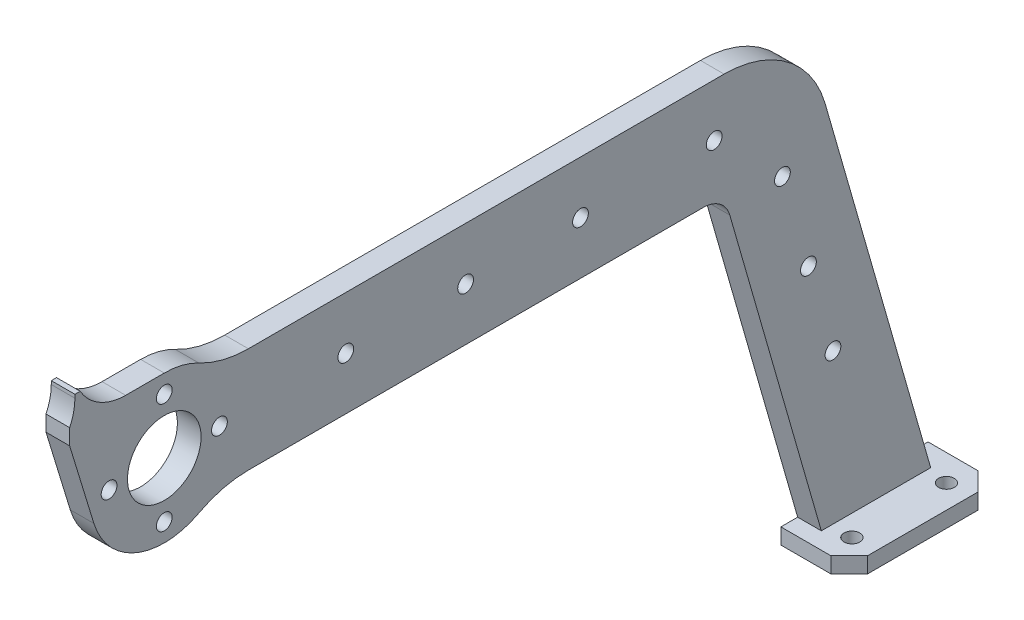
SolidWorks part; units mm, degrees
ref_plane "前视基准面" through (0, 0, 0) normal (0, 0, 1) x (1, 0, 0)
ref_plane "上视基准面" through (0, 0, 0) normal (0, 1, 0) x (1, 0, 0)
ref_plane "右视基准面" through (0, 0, 0) normal (1, 0, 0) x (0, 0, -1)
sketch "草图1" plane through (0, 0, 0) normal (1, 0, 0) x (0, 0, -1)
  line L2 (107.5854, -13.768) -> (125, -74.5)
  line L3 (125, -74.5) -> (145.806, -74.5)
  line L4 (145.806, -74.5) -> (125.7302, -4.4873)
  line L5 (106.5049, 10) -> (16, 10)
  line L7 (16, -10) -> (102.5851, -10)
  line L8 (135.8126, -75.9286) -> (111.4936, 8.8819) construction
  line L9 (0, 14) -> (-18, 14)
  line L10 (-18, 14) -> (-18, 11)
  line L11 (-18, 11) -> (-13.3889, -4.091)
  arc A0 (6.5882, 12.3529) -> (6.5882, -12.3529) centre (0, 0) ccw
  circle A1 centre (0, 0) radius 10.5 construction
  circle A2 centre (0, 0) radius 7
  circle A3 centre (0, 10.5) radius 1.5
  arc A7 (125.7302, -4.4873) -> (106.5049, 10) centre (106.5049, -10) ccw
  arc A8 (102.5851, -10) -> (107.5854, -13.768) centre (102.5851, -15.2018) cw
  arc A15 (16, 10) -> (6.5882, 12.3529) centre (16, 30) cw
  arc A16 (16, -10) -> (6.5882, -12.3529) centre (16, -30) ccw
  circle A17 centre (10.5, 0) radius 1.5
  circle A18 centre (0, -10.5) radius 1.5
  circle A19 centre (-10.5, 0) radius 1.5
  point P25 (0, 0)
  point P36 (135.403, -74.5)
  point P43 (9.798, 7.7889)
  point P50 (9.798, -10)
  dimension "D1" = 28
  dimension "D3" = 14
  dimension "D4" = 3
  dimension "D9" = 20
  dimension "D13" = 4
  dimension "D24" = 20
  dimension "D25" = 20
  dimension "D5" = 21
  dimension "D6" = 106
  dimension "D7" = 20
  dimension "D8" = 125
  dimension "D10" = 74.5
  dimension "D11" = 20
  dimension "D12" = 20.806
  dimension "D21" = 18
  dimension "D22" = 3
extrude "凸台-拉伸1" add sketch "草图1" along normal mid plane 4.5 contours A16 L7 A8 L2 L3 L4 A7 L5 A15 A0 A18 A17 A3 A2 | A0 L9 L10 L11 | A16 A0 region at (0, -9.5886, -106.815) region at (0, 9.7023, 13.097)
sketch "草图5" plane through (0, -74.5, 0) normal (0, -1, 0) x (1, 0, 0)
  line L0 (-2.25, -107.5854) -> (-2.25, -125) construction
  line L1 (-2.25, -121.806) -> (10.75, -121.806)
  line L2 (-2.25, -121.806) -> (-2.25, -149.806)
  line L3 (-2.25, -149.806) -> (10.75, -149.806)
  line L4 (10.75, -121.806) -> (10.75, -149.806)
  line L5 (2.25, -145.806) -> (-2.25, -145.806) construction
  dimension "D1" = 13
  dimension "D2" = 28
  dimension "D3" = 4
extrude "凸台-拉伸3" add sketch "草图5" along normal blind 3
sketch "草图6" plane through (0, -74.5, 0) normal (0, 1, 0) x (1, 0, 0)
  line L0 (10.75, 135.806) -> (-2.25, 135.806) construction
  line L1 (10.75, 149.806) -> (10.75, 121.806) construction
  line L2 (-2.25, 145.806) -> (-2.25, 125.7302) construction
  line L5 (2.25, 145.806) -> (2.25, 125.7302) construction
  circle A0 centre (6.25, 144.806) radius 1.5
  circle A1 centre (6.25, 126.806) radius 1.5
  dimension "D3" = 3
  dimension "D1" = 9
  dimension "D2" = 4
extrude "切除-拉伸2" cut sketch "草图6" against normal through all
sketch "草图7" plane through (2.25, 0, 0) normal (1, 0, 0) x (0, 0, -1)
  line L1 (0, 14) -> (-18, 14) construction
  line L2 (-17.0011, 14) -> (-17.0011, 18.9987)
  line L3 (-17.0011, 18.9987) -> (-16.0023, 18.9987)
  line L4 (-16.0023, 18.9987) -> (-16.0023, 14)
  line L5 (-16.0023, 14) -> (-17.0011, 14)
extrude "凸台-拉伸4" add sketch "草图7" against normal up to vertex (4.5 mm away) up to point (-2.25, 14, 0)
fillet "圆角1" radius 10 2 edges at (0, 14, 16.0023) (0, 14, 17.0011)
chamfer "倒角1" distance 3.5 angle 45 2 edges at (10.75, -76, -121.806) (10.75, -76, -149.806)
sketch "草图8" plane through (-2.25, 0, 0) normal (-1, 0, 0) x (0, 0, 1)
  line L0 (-16, 10) -> (-16, -10) construction
  line L1 (-106.5049, 10) -> (-102.5851, -10) construction
  line L2 (-125.7302, -4.4873) -> (-107.5854, -13.768) construction
  line L3 (-122.2436, -64.8874) -> (-141.4689, -59.3746) construction
  line L4 (-107.5854, -13.768) -> (-125, -74.5) construction
  line L5 (-145.806, -74.5) -> (-125.7302, -4.4873) construction
  line L6 (-131.8562, -62.131) -> (-116.6578, -9.1276)
  line L7 (-104.545, 0) -> (-16, 0)
  arc A0 (-102.5851, -10) -> (-107.5854, -13.768) centre (-102.5851, -15.2018) ccw construction
  arc A1 (-116.6578, -9.1276) -> (-104.545, 0) centre (-104.545, -12.6009) cw
  dimension "D1" = 10
sketch "草图9" plane through (-2.25, 0, 0) normal (-1, 0, 0) x (0, 0, 1)
  line L0 (-131.8562, -62.131) -> (-116.6578, -9.1276) construction
  line L1 (-104.545, 0) -> (-16, 0) construction
  point P0 (-127.2141, -45.9418)
  point P1 (-122.5496, -29.6747)
  point P4 (-104.6157, 0)
  point P5 (-79.1822, 0)
  point P8 (-57.3282, 0)
  point P9 (-34.5323, 0)
  point P11 (-117.6028, -12.4233)
sketch "草图10" plane through (-2.25, 0, 0) normal (-1, 0, 0) x (0, 0, 1)
  circle A0 centre (-34.5323, 0) radius 1.5
  dimension "D1" = 3
extrude "切除-拉伸3" cut sketch "草图10" against normal blind 10
pattern_sketch "草图阵列1" of "切除-拉伸3" driven by "草图9"
